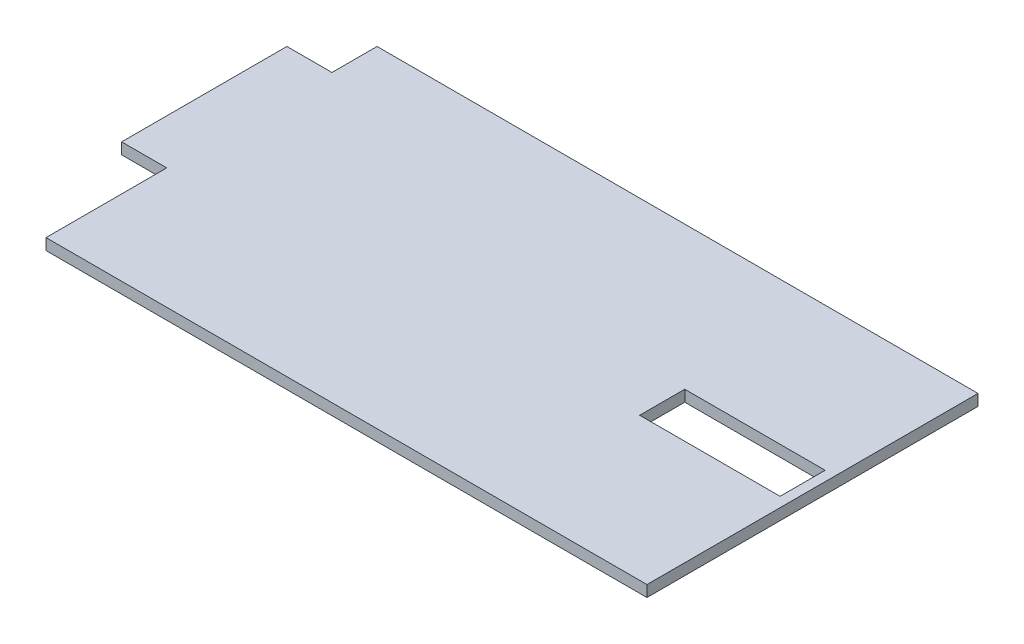
SolidWorks part; units mm, degrees
ref_plane "Front Plane" through (0, 0, 0) normal (0, 0, 1) x (1, 0, 0)
ref_plane "Top Plane" through (0, 0, 0) normal (0, 1, 0) x (1, 0, 0)
ref_plane "Right Plane" through (0, 0, 0) normal (1, 0, 0) x (0, 0, -1)
sketch "Sketch2" plane through (0, 0, 0) normal (0, 1, 0) x (1, 0, 0)
  line L0 (0, -6) -> (-6, -6)
  line L1 (0, 0) -> (80, 0)
  line L2 (0, 0) -> (0, -6)
  line L3 (0, -44.07) -> (80, -44.07)
  line L5 (-6, -6) -> (-6, -28)
  line L6 (-6, -28) -> (0, -28)
  line L7 (80, 0) -> (80, -36.6386) construction
  line L11 (0, -28) -> (0, -44.07)
  line L13 (8.7933, 0) -> (8.7933, -44.07) construction
  line L14 (8.7933, -22.035) -> (80, -22.035) construction
  line L15 (60, -19.035) -> (60, -25.035)
  line L16 (60, -25.035) -> (78.689, -25.035)
  line L18 (60, -19.035) -> (78.689, -19.035)
  line L19 (80, 0) -> (80, -44.07)
  line L20 (78.689, -19.035) -> (78.689, -25.035)
  point P24 (80, -25.035)
  point P25 (100, -22.035)
  point P26 (60, -22.035)
  dimension "D1" = 80
  dimension "D2" = 44.07
  dimension "D3" = 6
  dimension "D4" = 22
  dimension "D5" = 6
  dimension "D6" = 20
  dimension "D7" = 3
extrude "Boss-Extrude1" add sketch "Sketch2" along normal blind 1.5
